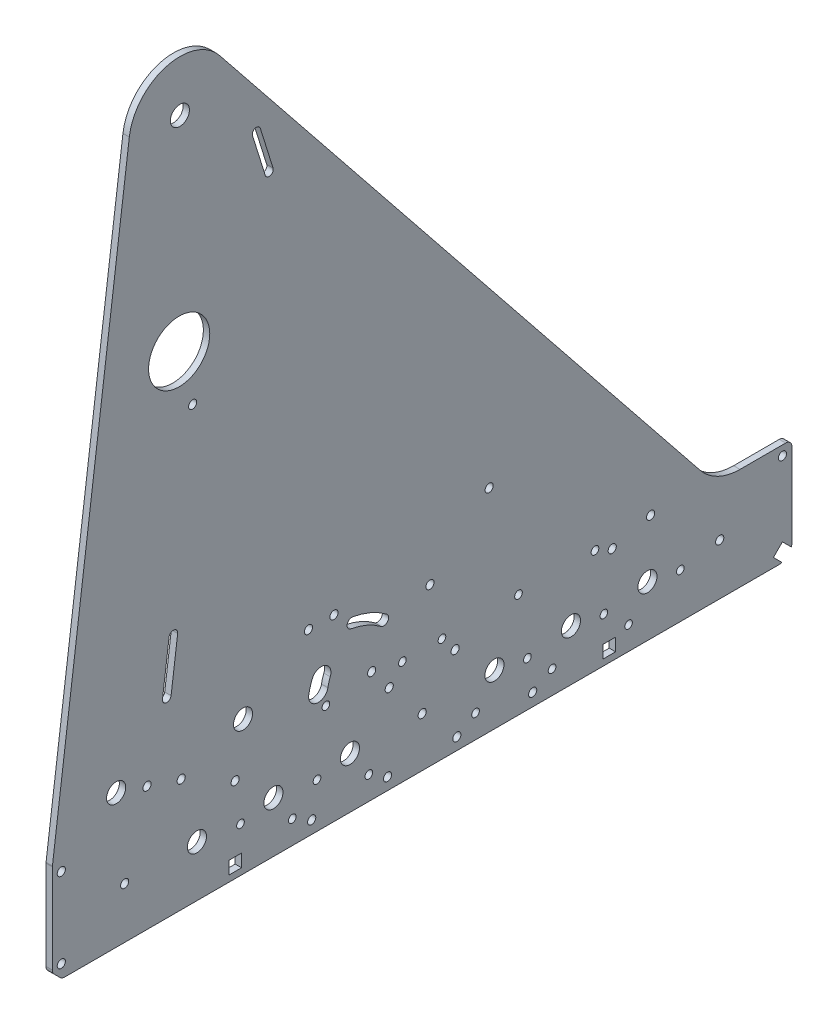
SolidWorks part; units mm, degrees
ref_plane "Front Plane" through (0, 0, 0) normal (0, 0, 1) x (1, 0, 0)
ref_plane "Top Plane" through (0, 0, 0) normal (0, 1, 0) x (1, 0, 0)
ref_plane "Right Plane" through (0, 0, 0) normal (1, 0, 0) x (0, 0, -1)
sketch "Sketch1" plane through (0, 0, 0) normal (1, 0, 0) x (0, 0, -1)
  line L0 (-184.15, -24.6062) -> (184.15, -24.6062)
  line L1 (184.15, -24.6062) -> (184.15, 26.1938)
  line L2 (184.15, 26.1938) -> (146.05, 26.1937)
  line L5 (-145.839, 321.5609) -> (-184.15, 26.1938)
  line L6 (-184.15, 26.1938) -> (-184.15, -24.6062)
  line L7 (-184.15, 350.0437) -> (184.15, 350.0437) construction
  line L9 (146.05, 26.1937) -> (-100.8314, 334.1803)
  arc A0 (-100.8314, 334.1803) -> (-145.839, 321.5609) centre (-120.65, 318.2937) ccw
  point P8 (0, -24.6062)
  dimension "D1" = 368.3
  dimension "D7" = 25.4
  dimension "D2" = 50.8
  dimension "D3" = 38.1
  dimension "D4" = 24.6062
  dimension "D5" = 374.65
  dimension "D6" = 304.8
  dimension "D8" = 342.9
extrude "Boss-Extrude1" add sketch "Sketch1" along normal blind 3.175
chamfer "Chamfer1" distance 4.7625 angle 45 2 edges at (1.5875, -24.6062, 184.15) (1.5875, -24.6062, -184.15)
fillet "Fillet1" radius 25.4 1 edges at (1.5875, 26.1937, -146.05)
fillet "Fillet2" radius 3.175 2 edges at (1.5875, 26.1938, 184.15) (1.5875, 26.1938, -184.15)
fillet "Fillet3" radius 3.175 4 edges at (1.5875, -19.8438, -184.15) (1.5875, -24.6062, -179.3875) (1.5875, -19.8437, 184.15) (1.5875, -24.6062, 179.3875)
sketch "Sketch30" plane through (3.175, 0, 0) normal (1, 0, 0) x (0, 0, -1)
  circle A8 centre (-89.211, 42.2593) radius 4.7625
  circle A9 centre (-25.1593, 30.6938) radius 2.032
  arc A10 (-51.7173, 35.4892) -> (-50.2741, 40.5715) centre (-25.1593, 30.6938) cw construction
  arc A11 (-54.7652, 42.3379) -> (-56.4665, 36.3468) centre (-25.1593, 30.6938) ccw
  arc A12 (-45.783, 38.8051) -> (-46.9681, 34.6317) centre (-25.1593, 30.6938) ccw
  arc A13 (-45.783, 38.8051) -> (-54.7652, 42.3379) centre (-50.2741, 40.5715) ccw
  arc A14 (-56.4665, 36.3468) -> (-46.9681, 34.6317) centre (-51.7173, 35.4892) ccw
  arc A15 (-34.9881, 56.6661) -> (-19.1131, 49.8125) centre (-41.7582, 19.1724) cw construction
  arc A16 (-17.6789, 51.753) -> (-34.5594, 59.0407) centre (-41.7582, 19.1724) ccw
  arc A17 (-20.5473, 47.8719) -> (-35.4169, 54.2915) centre (-41.7582, 19.1724) ccw
  arc A18 (-20.5473, 47.8719) -> (-17.6789, 51.753) centre (-19.1131, 49.8125) ccw
  arc A19 (-34.5594, 59.0407) -> (-35.4169, 54.2915) centre (-34.9881, 56.6661) ccw
  arc A20 (-19.1131, 49.8125) -> (-34.9881, 56.6661) centre (-41.7582, 19.1724) ccw construction
  circle A21 centre (94.6345, 23.8125) radius 2.032
  circle A22 centre (-56.6241, 64.5541) radius 2.032
  circle A23 centre (-43.9241, 64.5541) radius 2.032
  circle A24 centre (-56.6241, 64.5541) radius 1.905 construction
  circle A25 centre (-43.9241, 64.5541) radius 1.905 construction
  point P7 (-51.1204, 38.0658)
  point P19 (-26.6567, 54.1518)
  dimension "D2" = 9.652
  dimension "D4" = 4.064
  dimension "D1" = 4.064
  dimension ".375" = 9.525
  dimension "D3" = 4.826
extrude "Cut-Extrude9" cut sketch "Sketch30" against normal through all
sketch "Sketch16" plane through (3.175, 0, 0) normal (1, 0, 0) x (0, 0, -1)
  circle A0 centre (112.1746, 0.7937) radius 4.7625
  circle A1 centre (74.0746, 0.7937) radius 4.7625
  circle A2 centre (35.9746, 0.7937) radius 4.7625
  circle A3 centre (-35.9746, 0.7938) radius 4.7625
  circle A4 centre (-74.0746, 0.7938) radius 4.7625
  circle A5 centre (-112.1746, 0.7937) radius 4.7625
  dimension "D1" = 9.525
  dimension "D2" = 9.525
extrude "Cut-Extrude1" cut sketch "Sketch16" against normal up to next
sketch "Sketch25" plane through (3.175, 0, 0) normal (1, 0, 0) x (0, 0, -1)
  circle A0 centre (102.7672, -13.0003) radius 1.905 construction
  circle A1 centre (86.0486, 27.3622) radius 1.905 construction
  circle A2 centre (128.5804, -2.3081) radius 1.905 construction
  circle A3 centre (102.7672, -13.0003) radius 1.905
  circle A4 centre (86.0486, 27.3622) radius 1.905
  circle A5 centre (128.5804, -2.3081) radius 1.905
  circle A6 centre (64.6672, -13.0003) radius 1.905 construction
  circle A8 centre (-9.8486, 27.3622) radius 1.905 construction
  circle A10 centre (-47.9486, 27.3622) radius 1.905 construction
  circle A11 centre (-90.4804, -2.3081) radius 1.905 construction
  circle A12 centre (-64.6672, -13.0003) radius 1.905 construction
  circle A14 centre (-52.3804, -2.3081) radius 1.905 construction
  circle A15 centre (-26.5672, -13.0003) radius 1.905 construction
  circle A16 centre (9.8486, 27.3622) radius 1.905 construction
  circle A17 centre (26.5672, -13.0003) radius 1.905 construction
  circle A18 centre (47.9486, 27.3622) radius 1.905 construction
  circle A19 centre (52.3804, -2.3081) radius 1.905 construction
  circle A20 centre (90.4804, -2.3081) radius 1.905 construction
  circle A21 centre (-9.8486, 27.3622) radius 1.905
  circle A23 centre (-47.9486, 27.3622) radius 1.905
  circle A24 centre (-90.4804, -2.3081) radius 1.905
  circle A25 centre (-64.6672, -13.0003) radius 1.905
  circle A27 centre (-52.3804, -2.3081) radius 1.905
  circle A28 centre (-26.5672, -13.0003) radius 1.905
  circle A29 centre (9.8486, 27.3622) radius 1.905
  circle A30 centre (26.5672, -13.0003) radius 1.905
  circle A31 centre (47.9486, 27.3622) radius 1.905
  circle A32 centre (64.6672, -13.0003) radius 1.905
  circle A33 centre (52.3804, -2.3081) radius 1.905
  circle A34 centre (90.4804, -2.3081) radius 1.905
extrude "Cut-Extrude4" cut sketch "Sketch25" against normal up to next
sketch "Sketch23" plane through (3.175, 0, 0) normal (1, 0, 0) x (0, 0, -1)
  point P0 (-55.0246, -18.3223)
  point P6 (-93.1246, 17.5943)
  point P9 (-17.2515, -18.6426)
  point P12 (-16.4124, 19.3854)
  point P15 (16.4124, 19.3854)
  point P18 (17.2515, -18.6426)
  point P21 (55.0246, -18.3223)
  point P35 (3.8736, 53.6853)
  point P38 (113.7728, 28.6594)
  point P41 (-137.0088, 37.226)
  point P44 (-179.705, 21.7487)
  point P47 (-179.705, -18.0026)
  point P50 (179.3875, 21.4312)
hole_wizard "#8 (0.16) Diameter Hole1" positions "Sketch23" profile "Sketch24" hole size "#8" standard "ANSI Inch" end condition up to next
sketch "Sketch24" plane through (3.175, -18.3223, 55.0246) normal (0, 1, 0) x (0, 0, -1)
  line L0 (0, 0) -> (0, 3.175)
  line L1 (0, 3.175) -> (2.032, 3.175)
  line L2 (2.032, 3.175) -> (2.032, 0)
  line L5 (2.032, 0) -> (0, 0)
  line L11 (0, -6.35) -> (0, 107.95) construction
  dimension "Thru Hole Dia." = 4.064
  dimension "Thru Hole Depth" = 3.175
sketch "Sketch22" plane through (3.175, 0, 0) normal (1, 0, 0) x (0, 0, -1)
  line L0 (-96.2996, -15.1473) -> (-89.9496, -15.1473) construction
  line L1 (-96.2996, -15.1473) -> (-89.9496, -15.1473)
  line L2 (-96.2996, -15.1473) -> (-96.2996, -21.4973)
  line L3 (-96.2996, -21.4973) -> (-89.9496, -21.4973)
  line L4 (-89.9496, -15.1473) -> (-89.9496, -21.4973)
  line L5 (-96.2996, -15.1473) -> (-89.9496, -21.4973) construction
  line L6 (-96.2996, -21.4973) -> (-89.9496, -15.1473) construction
  line L7 (-89.9496, -15.1473) -> (-89.9496, -19.8734) construction
  line L77 (179.3875, -24.6062) -> (183.8776, -20.1161)
  line L78 (179.3875, -24.6062) -> (174.8974, -20.1161)
  line L79 (183.8776, -20.1161) -> (179.3875, -15.626)
  line L80 (174.8974, -20.1161) -> (179.3875, -15.626)
  line L81 (180.3174, -23.6763) -> (183.2201, -20.7737) construction
  line L82 (-178.0724, -24.6062) -> (178.0724, -24.6062) construction
  line L84 (89.9496, -21.4973) -> (96.2996, -21.4973)
  line L85 (89.9496, -21.4973) -> (89.9496, -15.1473)
  line L86 (89.9496, -15.1473) -> (96.2996, -15.1473)
  line L87 (96.2996, -21.4973) -> (96.2996, -15.1473)
  line L88 (89.9496, -21.4973) -> (96.2996, -15.1473) construction
  line L89 (89.9496, -15.1473) -> (96.2996, -21.4973) construction
  point P0 (-93.1246, -18.3223)
  point P19 (93.1246, -18.3223)
  dimension "D1" = 6.35
  dimension "D2" = 6.35
extrude "Cut-Extrude3" cut sketch "Sketch22" against normal up to next
sketch "Sketch21" plane through (3.175, 0, 0) normal (1, 0, 0) x (0, 0, -1)
  circle A0 centre (-148.1579, 0.7937) radius 2.032
  circle A2 centre (0, 0) radius 2.032
  circle A3 centre (148.1579, 0.7938) radius 2.032
  dimension "D1" = 4.064
extrude "Cut-Extrude2" cut sketch "Sketch21" against normal up to next
sketch "Sketch26" plane through (3.175, 0, 0) normal (1, 0, 0) x (0, 0, -1)
  line L0 (-145.839, 321.5609) -> (-184.1236, 26.3971) construction
  line L1 (-178.0724, -24.6062) -> (178.0724, -24.6062) construction
  circle A0 centre (-121.0218, 216.6937) radius 15.24
  dimension "D1" = 30.48
  dimension "D2" = 38.1
  dimension "D3" = 241.3
extrude "Cut-Extrude5" cut sketch "Sketch26" against normal through all
sketch "Sketch27" plane through (3.175, 0, 0) normal (1, 0, 0) x (0, 0, -1)
  circle A0 centre (-120.65, 318.2937) radius 4.7625
  dimension "D1" = 9.525
extrude "Cut-Extrude6" cut sketch "Sketch27" against normal through all
sketch "Sketch28" plane through (3.175, 0, 0) normal (1, 0, 0) x (0, 0, -1)
  line L0 (-120.65, 318.2937) -> (-103.5612, 277.2599) construction
  line L1 (-103.5612, 277.2599) -> (-86.3654, 258.566) construction
  line L2 (-86.3654, 258.566) -> (-90.1612, 246.4465) construction
  line L3 (-90.1612, 246.4465) -> (-93.9569, 234.327) construction
  line L4 (-145.839, 321.5609) -> (-184.1236, 26.3971) construction
  circle A0 centre (-93.9569, 234.327) radius 2.032
  circle A1 centre (-90.1612, 246.4465) radius 2.032
  circle A2 centre (-86.3654, 258.566) radius 2.0955
  circle A3 centre (-103.5612, 277.2599) radius 2.032
  dimension "D4" = 4.064
  dimension "D5" = 4.191
  dimension "D6" = 4.064
  dimension "D1" = 25.4
  dimension "D2" = 44.45
  dimension "D3" = 12.7
  dimension "D7" = 30
  dimension "D8" = 120
  dimension "D9" = 160
extrude "Cut-Extrude7" [suppressed] cut sketch "Sketch28" against normal through all
sketch "Sketch29" plane through (3.175, 0, 0) normal (1, 0, 0) x (0, 0, -1)
  line L1 (-82.55, 292.1) -> (-76.2, 271.78) construction
  line L2 (-80.6105, 292.7061) -> (-74.2605, 272.3861)
  line L3 (-84.4895, 291.4939) -> (-78.1395, 271.1739)
  arc A4 (-80.6105, 292.7061) -> (-84.4895, 291.4939) centre (-82.55, 292.1) ccw
  arc A5 (-78.1395, 271.1739) -> (-74.2605, 272.3861) centre (-76.2, 271.78) ccw
  point P0 (-81.8996, 292.572)
  point P8 (-79.375, 281.94)
  dimension "D1" = 271.78
  dimension "D2" = 2.032
  dimension "D3" = 76.2
  dimension "D4" = 82.55
  dimension "D5" = 292.1
sketch "Sketch31" plane through (0, 0, 0) normal (-1, 0, 0) x (0, 0, 1)
  circle A1 centre (114.3, 190.5) radius 2.032
  dimension "D1" = 114.3
  dimension "D6" = 4.064
  dimension "D2" = 190.5
extrude "Cut-Extrude10" cut sketch "Sketch31" against normal through all
sketch "Sketch34" plane through (0, 0, 0) normal (-1, 0, 0) x (0, 0, 1)
  line L3 (123.9045, 95.7355) -> (127.1716, 70.5465) construction
  line L4 (126.0455, 96.0132) -> (129.3127, 70.8242)
  line L5 (121.7634, 95.4578) -> (125.0306, 70.2688)
  line L6 (145.839, 321.5609) -> (184.1236, 26.3971) construction
  arc A2 (126.0455, 96.0132) -> (121.7634, 95.4578) centre (123.9045, 95.7355) ccw
  arc A3 (125.0306, 70.2688) -> (129.3127, 70.8242) centre (127.1716, 70.5465) ccw
  point P9 (125.538, 83.141)
  point P18 (114.3, 190.5)
  dimension "D8" = 4.318
  dimension "D6" = 50.8
  dimension "D7" = 25.4
  dimension "D9" = 95.25
extrude "Cut-Extrude12" cut sketch "Sketch34" against normal through all
sketch "Sketch37" plane through (3.175, 0, 0) normal (1, 0, 0) x (0, 0, -1)
  circle A0 centre (33.3375, 80.645) radius 2.032
  circle A8 centre (0, 0) radius 2.032 construction
  dimension "D1" = 4.064
  dimension "D2" = 33.3375
  dimension "D3" = 80.645
extrude "Cut-Extrude13" cut sketch "Sketch37" against normal through all
sketch "Sketch38" plane through (3.175, 0, 0) normal (1, 0, 0) x (0, 0, -1)
  line L0 (-184.15, 25.9887) -> (-184.15, -18.5286) construction
  line L1 (-178.0724, -24.6062) -> (178.0724, -24.6062) construction
  circle A0 centre (-152.4, 42.0688) radius 4.7625
  dimension "D1" = 31.75
  dimension "D3" = 9.525
  dimension "D2" = 66.675
extrude "Cut-Extrude14" cut sketch "Sketch38" against normal through all
extrude "Cut-Extrude15" cut sketch "Sketch29" against normal through all
sketch "Sketch40" plane through (3.175, 0, 0) normal (1, 0, 0) x (0, 0, -1)
  circle A0 centre (-120.015, 31.75) radius 2.032
  dimension "D1" = 4.064
  dimension "D2" = 120.015
  dimension "D3" = 31.75
extrude "Cut-Extrude16" cut sketch "Sketch40" against normal through all
